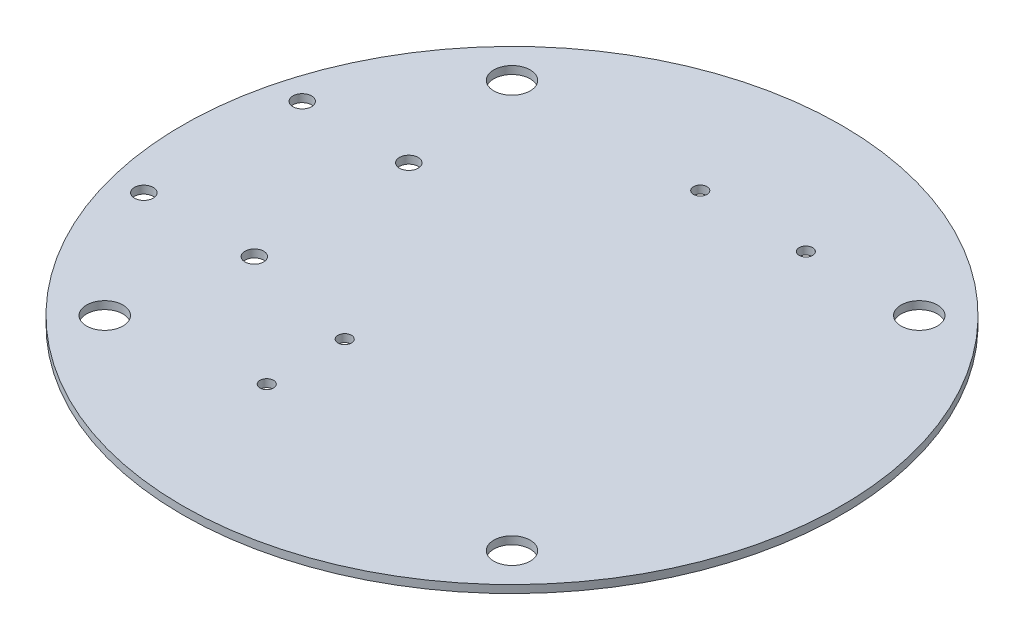
SolidWorks part; units mm, degrees
ref_plane "Front Plane" through (0, 0, 0) normal (0, 0, 1) x (1, 0, 0)
ref_plane "Top Plane" through (0, 0, 0) normal (0, 1, 0) x (1, 0, 0)
ref_plane "Right Plane" through (0, 0, 0) normal (1, 0, 0) x (0, 0, -1)
sketch "Sketch1" plane through (0, 0, 0) normal (0, 1, 0) x (1, 0, 0)
  circle A0 centre (0, 0) radius 63.4
  dimension "PCBdiam" = 126.8
extrude "Boss-Extrude1" add sketch "Sketch1" along normal blind 1.5
hole_wizard "M6 Clearance Hole1" positions "Sketch2" profile "Sketch4" hole size "M6" standard "ANSI Metric" end condition through all
sketch "Sketch2" plane through (0, 1.5, 0) normal (0, 1, 0) x (1, 0, 0)
  line L0 (0, 0) -> (-28.5457, 28.5457) construction
  line L1 (-39.1737, -39.1737) -> (0, 0) construction
  line L3 (0, 0) -> (-73.422, 0) construction
  circle A0 centre (0, 0) radius 63.4 construction
  ellipse E2 centre (-116.4291, -176.9435) end of major axis (-117.7556, -176.0714) minor radius 1.3748
  ellipse E3 centre (-116.4291, -176.9435) end of major axis (-115.1026, -177.8157) minor radius 1.3748
  point P7 (-39.1737, -39.1737)
  dimension "D1" = 0
  dimension "holeRadius" = 55.4
  dimension "D2" = 45
sketch "Sketch4" plane through (-39.1737, 1.5, 39.1737) normal (1, 0, 0) x (0, 0, 1)
  line L0 (0, 0) -> (0, 1.5)
  line L1 (0, 1.5) -> (3.5, 1.5)
  line L2 (3.5, 1.5) -> (3.5, 0)
  line L5 (3.5, 0) -> (0, 0)
  line L11 (0, -6.35) -> (0, 107.95) construction
  dimension "Thru Hole Dia." = 7
  dimension "Thru Hole Depth" = 1.5
pattern_circular "CirPattern1" count 4 over 360 about axis through (0, 1.5, 0) along (0, -1, 0) of "M6 Clearance Hole1"
sketch "Teensy Outline" plane through (0, 1.5, 0) normal (0, 1, 0) x (1, 0, 0)
  line L1 (-29.654, 48.4) -> (-12, 48.4)
  line L2 (-29.654, 48.4) -> (-29.654, -10.02)
  line L3 (-29.654, -10.02) -> (-12, -10.02)
  line L4 (-12, 48.4) -> (-12, -10.02)
  circle A1 centre (0, 0) radius 63.4 construction
  dimension "D1" = 17.654
  dimension "D2" = 58.42
  dimension "D3" = 12
  dimension "D4" = 15
sketch "BMP390 Outline" plane through (0, 1.5, 0) normal (0, 1, 0) x (1, 0, 0)
  line L0 (17.61, 52.4) -> (-5.25, 52.4) construction
  line L2 (20.15, 53.74) -> (-5.25, 53.74)
  line L3 (-5.25, 53.74) -> (-5.25, 35.96)
  line L4 (20.15, 35.96) -> (-5.25, 35.96)
  line L6 (20.15, 53.74) -> (20.15, 35.96)
  line L7 (17.61, 52.4) -> (17.61, 35.96) construction
  line L8 (-29.654, 48.4) -> (-12, 48.4) construction
  line L9 (-12, 48.4) -> (-12, -10.02) construction
  dimension "D1" = 17.78
  dimension "D2" = 25.4
  dimension "D3" = 1.34
  dimension "D4" = 4
  dimension "D5" = 6.75
  dimension "D6" = 5.08
sketch "NEO-6M Outline" plane through (0, 1.5, 0) normal (0, 1, 0) x (1, 0, 0)
  line L0 (-50.84, 17.78) -> (-50.84, 15.24) construction
  line L1 (-58.34, 17.78) -> (-32, 17.78)
  line L2 (-58.34, 17.78) -> (-58.34, -17.78)
  line L3 (-58.34, -17.78) -> (-32, -17.78)
  line L4 (-32, 17.78) -> (-32, -17.78)
  line L5 (-50.84, 15.24) -> (-39.5, 15.24) construction
  line L6 (-39.5, 15.24) -> (-39.5, 17.78) construction
  point P4 (-32, 0)
  point P9 (-45.17, 15.24)
  point P11 (-45.17, 17.78)
  dimension "D1" = 26.34
  dimension "D2" = 35.56
  dimension "D3" = 32
  dimension "D4" = 7.5
  dimension "D5" = 2.54
sketch "Xbee outline" plane through (0, 1.5, 0) normal (0, 1, 0) x (1, 0, 0)
  line L0 (9, 6.5) -> (26, 6.5) construction
  line L1 (26, 1.875) -> (26, 11.125)
  line L2 (26, 11.125) -> (19.5, 18.75)
  line L3 (19.5, 18.75) -> (-7, 18.75)
  line L4 (-7, 18.75) -> (-7, -5.75)
  line L5 (19.5, -5.75) -> (-7, -5.75)
  line L6 (26, 1.875) -> (19.5, -5.75)
  line L7 (0, 0) -> (72.9219, 0) construction
  line L9 (-12, 48.4) -> (-12, -10.02) construction
  line L10 (61, 12) -> (26, 12) construction
  line L11 (61, 12) -> (61, 1) construction
  line L12 (61, 1) -> (26, 1) construction
  line L13 (26, 12) -> (26, 1) construction
  point P7 (-7, 6.5)
  point P11 (26, 6.5)
  dimension "D1" = 24.5
  dimension "D2" = 33
  dimension "D3" = 26.5
  dimension "D4" = 9.25
  dimension "D5" = 16
  dimension "D6" = 35
  dimension "D7" = 11
  dimension "D8" = 6.5
  dimension "D9" = 5
sketch "Accel, gyro outline" plane through (0, 1.5, 0) normal (0, 1, 0) x (1, 0, 0)
  line L0 (47.32, 31.44) -> (27, 31.44) construction
  line L1 (52.4, 32.78) -> (27, 32.78)
  line L2 (27, 32.78) -> (27, 15)
  line L3 (52.4, 15) -> (27, 15)
  line L4 (52.4, 32.78) -> (52.4, 15)
  line L5 (47.32, 31.44) -> (47.32, 16.34) construction
  line L6 (27, 23.89) -> (52.4, 23.89) construction
  line L7 (47.32, 16.34) -> (27, 16.34) construction
  dimension "D1" = 17.78
  dimension "D2" = 25.4
  dimension "D3" = 1.34
  dimension "D4" = 5.08
  dimension "D5" = 15
  dimension "D6" = 27
sketch "Sketch17" plane through (0, 1.5, 0) normal (0, 1, 0) x (1, 0, 0)
  line L0 (-29.654, -23.1737) -> (-36.154, -23.1737) construction
  line L1 (-29.654, -17.1737) -> (-9.654, -17.1737)
  line L2 (-29.654, -17.1737) -> (-29.654, -37.1737)
  line L3 (-29.654, -37.1737) -> (-9.654, -37.1737)
  line L4 (-9.654, -17.1737) -> (-9.654, -37.1737)
  line L5 (-36.154, -23.1737) -> (-36.154, -31.1737) construction
  line L6 (-36.154, -31.1737) -> (-29.654, -31.1737) construction
  line L7 (-29.654, 48.4) -> (-29.654, -10.02) construction
  circle A0 centre (-39.1737, -39.1737) radius 3.5 construction
  point P8 (-36.154, -27.1737)
  point P9 (-29.654, -27.1737)
  dimension "D1" = 20
  dimension "D2" = 20
  dimension "D3" = 6.5
  dimension "D4" = 8
  dimension "D5" = 0
  dimension "D6" = 2
hole_wizard "M2 Clearance Hole1" positions "Sketch20" profile "Sketch19" hole size "M2" standard "ANSI Metric" end condition through all
sketch "Sketch20" plane through (0, 1.5, 0) normal (0, 1, 0) x (1, 0, 0)
  circle A0 centre (-2.71, 38.93) radius 1.2493 construction
  circle A1 centre (17.61, 38.93) radius 1.2493 construction
  circle A2 centre (-12.154, -20.0273) radius 1.25 construction
  circle A3 centre (-12.154, -20.0273) radius 1.25 construction
  circle A4 centre (-12.154, -35.0273) radius 1.25 construction
  circle A5 centre (-12.154, -35.0273) radius 1.25 construction
  point P1 (-2.71, 38.93)
  point P7 (17.61, 38.93)
  point P13 (-12.154, -20.0273)
  point P16 (-12.154, -35.0273)
sketch "Sketch19" plane through (-2.71, 1.5, -38.93) normal (1, 0, 0) x (0, 0, 1)
  line L0 (0, 0) -> (0, 1.5)
  line L1 (0, 1.5) -> (1.3, 1.5)
  line L2 (1.3, 1.5) -> (1.3, 0)
  line L5 (1.3, 0) -> (0, 0)
  line L11 (0, -6.35) -> (0, 107.95) construction
  dimension "Thru Hole Dia." = 2.6
  dimension "Thru Hole Depth" = 1.5
hole_wizard "M3 Clearance Hole2" positions "Sketch21" profile "Sketch22" hole size "M3" standard "ANSI Metric" end condition through all
sketch "Sketch21" plane through (0, 1.5, 0) normal (0, 1, 0) x (1, 0, 0)
  point P0 (-55.8645, 15.5117)
  point P3 (-55.8645, -14.9683)
  point P6 (-34.6045, -14.9683)
  point P9 (-35.3665, 15.5117)
sketch "Sketch22" plane through (-55.8645, 1.5, -15.5117) normal (1, 0, 0) x (0, 0, 1)
  line L0 (0, 0) -> (0, 1.5)
  line L1 (0, 1.5) -> (1.8, 1.5)
  line L2 (1.8, 1.5) -> (1.8, 0)
  line L5 (1.8, 0) -> (0, 0)
  line L11 (0, -6.35) -> (0, 107.95) construction
  dimension "Thru Hole Dia." = 3.6
  dimension "Thru Hole Depth" = 1.5
